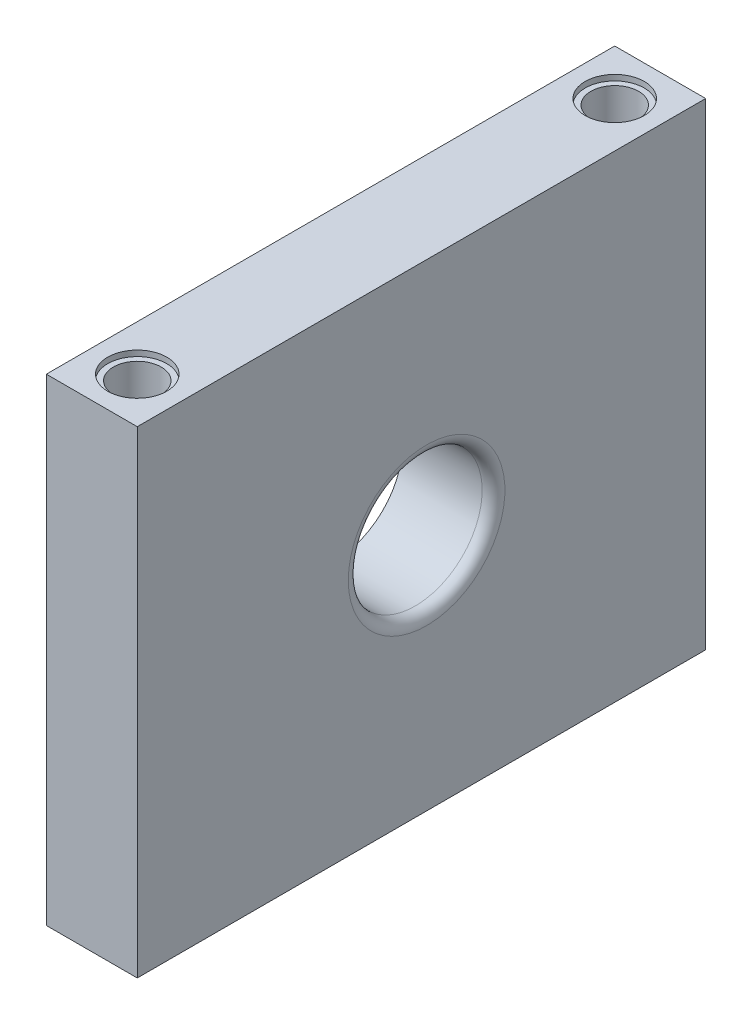
SolidWorks part; units mm, degrees
ref_plane "Front Plane" through (0, 0, 0) normal (0, 0, 1) x (1, 0, 0)
ref_plane "Top Plane" through (0, 0, 0) normal (0, 1, 0) x (1, 0, 0)
ref_plane "Right Plane" through (0, 0, 0) normal (1, 0, 0) x (0, 0, -1)
sketch "Sketch1" plane through (0, 0, 0) normal (0, 1, 0) x (1, 0, 0)
  line L1 (-10.223, 36.3848) -> (14.777, 36.3848)
  line L2 (-10.223, 36.3848) -> (-10.223, -13.6152)
  line L3 (-10.223, -13.6152) -> (14.777, -13.6152)
  line L4 (14.777, 36.3848) -> (14.777, -13.6152)
  circle A0 centre (1.277, 11.3848) radius 3.4
  dimension "D3" = 6.8
  dimension "D1" = 50
  dimension "D2" = 25
  dimension "D4" = 13.5
  dimension "D5" = 25
extrude "Boss-Extrude1" add sketch "Sketch1" along normal blind 3
sketch "Sketch2" plane through (-10.223, 0, 0) normal (-1, 0, 0) x (0, 0, 1)
  line L0 (18.15, 0) -> (-18.15, 0) construction
  line L1 (-36.3848, 3) -> (13.6152, 3)
  line L2 (-36.3848, 3) -> (-36.3848, 0)
  line L3 (-36.3848, 0) -> (13.6152, 0)
  line L4 (13.6152, 3) -> (13.6152, 0)
  line L5 (13.6152, 3) -> (13.6152, 0) construction
extrude "Boss-Extrude2" add sketch "Sketch2" along normal blind 8
sketch "Sketch3" plane through (0, 0, 0) normal (0, -1, 0) x (1, 0, 0)
  line L0 (-18.223, 13.6152) -> (14.777, 13.6152) construction
  line L1 (-18.223, -36.3848) -> (-10.223, -36.3848)
  line L2 (-18.223, -36.3848) -> (-18.223, 13.6152)
  line L3 (-18.223, 13.6152) -> (-10.223, 13.6152)
  line L4 (-10.223, -36.3848) -> (-10.223, 13.6152)
  dimension "D1" = 8
extrude "Boss-Extrude3" add sketch "Sketch3" along normal blind 42
sketch "Sketch4" plane through (0, 3, 0) normal (0, 1, 0) x (1, 0, 0)
  line L0 (-18.223, -13.6152) -> (-18.223, 36.3848) construction
  line L1 (14.777, 36.3848) -> (-18.223, 36.3848) construction
  line L2 (-18.223, -13.6152) -> (14.777, -13.6152) construction
  circle A0 centre (-14.223, 32.3848) radius 2.65
  circle A1 centre (-14.223, -9.6152) radius 2.65
  dimension "D2" = 5.3
  dimension "D4" = 5.3
  dimension "D5" = 4
  dimension "D6" = 4
  dimension "D1" = 4
  dimension "D3" = 4
extrude "Cut-Extrude1" cut sketch "Sketch4" against normal blind 0.5
ref_plane "Plane1" through (0, -19.5, 0) normal (0, 1, 0) x (1, 0, 0)
mirror "Mirror1" about plane through (0, -19.5, 0) normal (0, 1, 0) of "Cut-Extrude1"
sketch "Sketch5" plane through (-18.223, 0, 0) normal (-1, 0, 0) x (0, 0, 1)
  line L0 (18.15, 0) -> (-18.15, 0) construction
  line L1 (-6.9117, -24.2293) -> (-6.5773, -18.3498) construction
  line L2 (-6.5773, -18.3498) -> (-11.502, -15.1205) construction
  line L3 (-11.502, -15.1205) -> (-16.7609, -17.7707) construction
  line L4 (-16.7609, -17.7707) -> (-17.0952, -23.6502) construction
  line L5 (-17.0952, -23.6502) -> (-12.1706, -26.8795) construction
  line L6 (-12.1706, -26.8795) -> (-6.9117, -24.2293) construction
  circle A0 centre (-11.8363, -21) radius 5.1 construction
  circle A1 centre (-11.8363, -21) radius 5.889
  dimension "D1" = 21
  dimension "D2" = 10.2
extrude "Cut-Extrude2" cut sketch "Sketch5" against normal blind 9
fillet "Fillet2" radius 1 1 edges at (-10.223, -21, -5.9473)
ref_plane "Plane2" through (-1.723, 0, 0) normal (-1, 0, 0) x (0, 0, 1)
mirror "Mirror2" about plane through (-1.723, 0, 0) normal (-1, 0, 0) of "Cut-Extrude1"
sketch "Sketch6" plane through (0, 3, 0) normal (0, 1, 0) x (1, 0, 0)
  line L0 (1.277, 14.7848) -> (1.277, 7.9848) construction
  line L1 (14.777, -13.6152) -> (14.777, 36.3848) construction
  line L2 (14.777, 16.9444) -> (14.777, 5.8251)
  circle A0 centre (1.277, 11.3848) radius 3.4 construction
  circle A1 centre (1.277, 11.3848) radius 3.1
  circle A2 centre (1.277, 11.3848) radius 12.6
  arc A3 (14.777, 16.9444) -> (14.777, 5.8251) centre (1.277, 11.3848) ccw
  line M9 (14.777, -13.6152) -> (14.777, 36.3848)
  dimension "D1" = 25.2
  dimension "D2" = 2
extrude "Boss-Extrude4" add sketch "Sketch6" along normal blind 2 contours A3 A2 M9
fillet "Fillet4" radius 1 1 edges at (14.777, 5, -11.3848)
sketch "Sketch8" plane through (0, 3, 0) normal (0, 1, 0) x (1, 0, 0)
  line L0 (4.677, 11.3848) -> (-2.123, 11.3848) construction
  circle A0 centre (1.277, 11.3848) radius 3.4 construction
  circle A1 centre (1.277, 19.8848) radius 1.5898
  circle A2 centre (1.277, 2.8848) radius 1.7774
  point P9 (1.277, 11.3848)
  dimension "D1" = 8.5
  dimension "D2" = 8.5
extrude "Cut-Extrude3" cut sketch "Sketch8" against normal blind 10
sketch "Sketch9" plane through (0, 0, 13.6152) normal (0, 0, 1) x (1, 0, 0)
  line L1 (14.777, 0) -> (-34.2447, 0)
  line L2 (14.777, 0) -> (14.777, 20.9769)
  line L3 (14.777, 20.9769) -> (-34.2447, 20.9769)
  line L4 (-34.2447, 0) -> (-34.2447, 20.9769)
extrude "Cut-Extrude4" cut sketch "Sketch9" against normal through all
ref_plane "Plane3" through (0, 0, -11.3848) normal (0, 0, 1) x (1, 0, 0)
sketch "Sketch11" plane through (0, 0, 0) normal (0, 1, 0) x (1, 0, 0)
  circle A2 centre (-14.223, 32.3848) radius 2.1
  dimension "D1" = 4.2
extrude "Cut-Extrude5" cut sketch "Sketch11" against normal through all contours A2
mirror "Mirror3" about plane through (0, 0, -11.3848) normal (0, 0, 1) of "Cut-Extrude5"
sketch "Sketch14" plane through (0, 0, 0) normal (0, 1, 0) x (1, 0, 0)
  circle A0 centre (-14.223, -9.6152) radius 2.6
  dimension "D1" = 5.2
extrude "Cut-Extrude6" cut sketch "Sketch14" against normal blind 0.5
mirror "Mirror4" about plane through (0, 0, -11.3848) normal (0, 0, 1) of "Cut-Extrude6"
